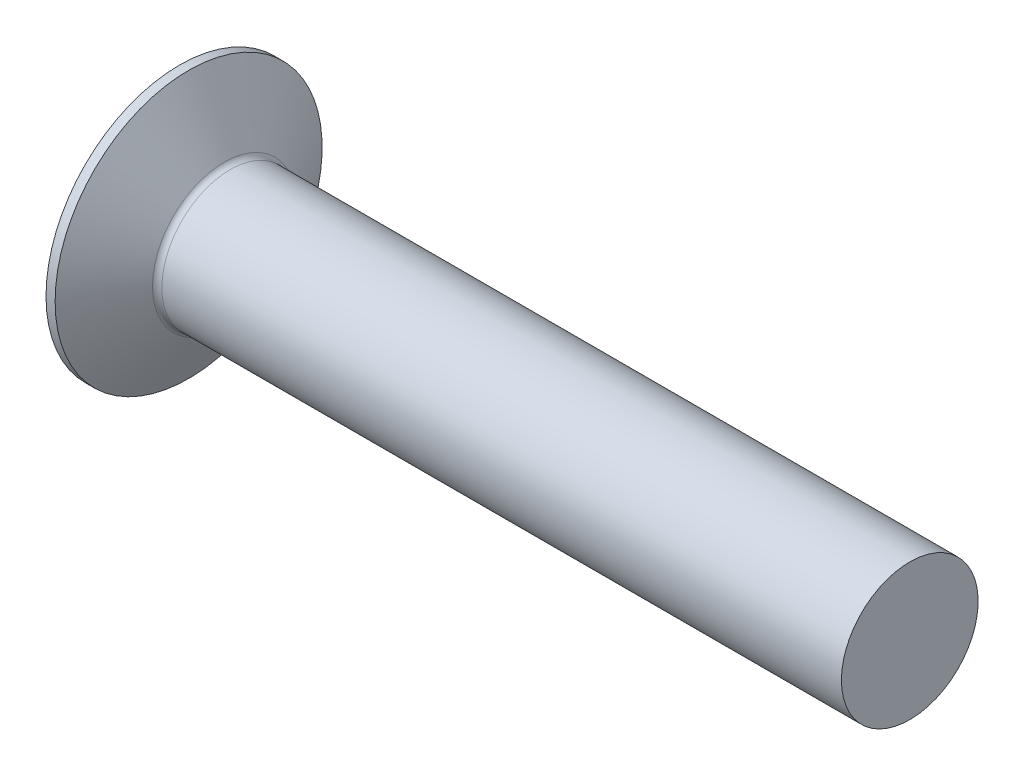
SolidWorks part; units mm, degrees
ref_plane "Front" through (0, 0, 0) normal (0, 0, 1) x (1, 0, 0)
ref_plane "Top" through (0, 0, 0) normal (0, 1, 0) x (1, 0, 0)
ref_plane "Right" through (0, 0, 0) normal (1, 0, 0) x (0, 0, -1)
sketch "Sketch1" plane through (0, 0, 0) normal (0, 0, 1) x (1, 0, 0)
  line L0 (-58.1433, 0) -> (17.5601, 0) construction
  line L1 (32.9775, 0) -> (32.9775, 3)
  line L2 (32.9775, 3) -> (3.1507, 3)
  line L3 (2.8909, 3.15) -> (1.3263, 5.86)
  line L4 (1.3263, 5.86) -> (0.9263, 5.86)
  line L5 (32.9775, 0) -> (0, 0)
  arc A0 (0.9263, 5.86) -> (0, 0) centre (19, 0) ccw
  arc A1 (3.1507, 3) -> (2.8909, 3.15) centre (3.1507, 3.3) cw
  point P12 (2.9775, 3)
  dimension "r" = 19
  dimension "r1" = 0.3
  dimension "d" = 6
  dimension "l" = 30
  dimension "D2" = 60
  dimension "K" = 0.4
  dimension "dk" = 11.72
revolve "Base-Revolve" add sketch "Sketch1" angle 360 about L0
